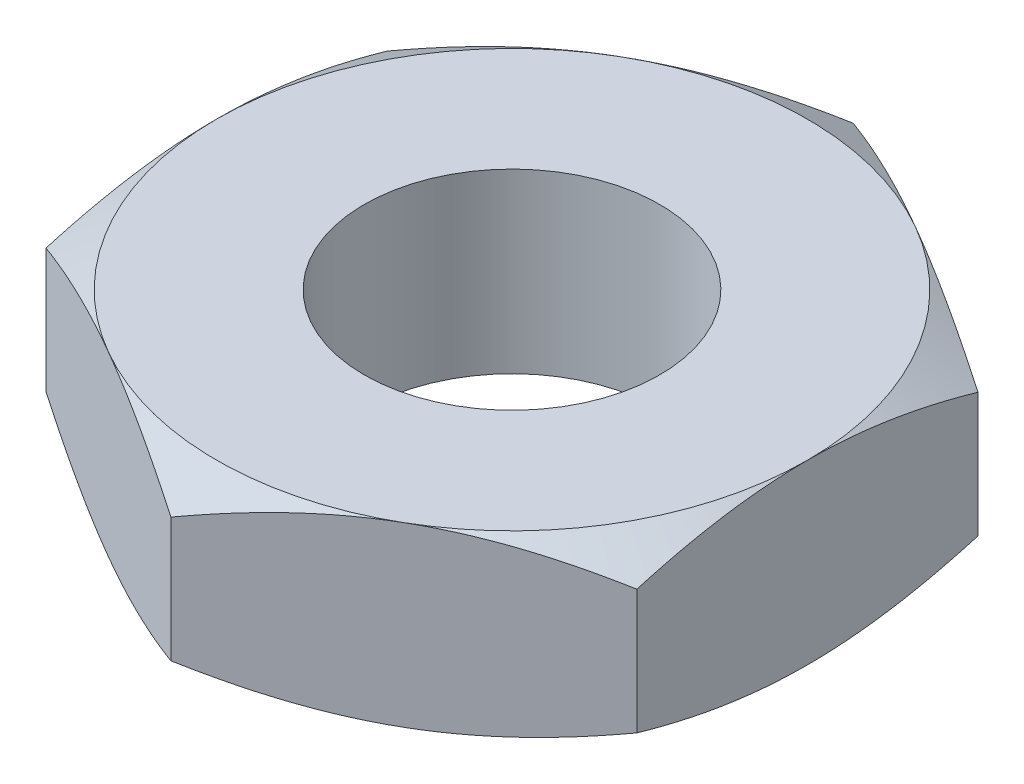
SolidWorks part; units mm, degrees
material "AISI 304"
ref_plane "Front Plane" through (0, 0, 0) normal (0, 0, 1) x (1, 0, 0)
ref_plane "Top Plane" through (0, 0, 0) normal (0, 1, 0) x (1, 0, 0)
ref_plane "Right Plane" through (0, 0, 0) normal (1, 0, 0) x (0, 0, -1)
sketch "Sketch1" plane through (0, 0, 0) normal (0, 1, 0) x (1, 0, 0)
  line L1 (-2, 1.1547) -> (-2, -1.1547)
  line L2 (-2, -1.1547) -> (0, -2.3094)
  line L3 (0, -2.3094) -> (2, -1.1547)
  line L4 (2, -1.1547) -> (2, 1.1547)
  line L5 (2, 1.1547) -> (0, 2.3094)
  line L6 (0, 2.3094) -> (-2, 1.1547)
  circle A0 centre (0, 0) radius 2 construction
  circle A1 centre (0, 0) radius 1
  dimension "Thread Size" = 2
  dimension "Hex" = 4
extrude "Boss-Extrude1" add sketch "Sketch1" along normal mid plane 1.2
sketch "Sketch2" plane through (0, 0.6, 0) normal (0, 1, 0) x (1, 0, 0)
  circle A0 centre (0, 0) radius 1 construction
  circle A1 centre (0, 0) radius 1
curve "Helix/Spiral1" [suppressed] pitch 0.4 height 1.6 turns 4 parameters "Pitch"=0.4
sketch "Sketch3" plane through (0, 0, 0) normal (1, 0, 0) x (0, 0, -1)
  line L0 (0.7402, 0.8) -> (1, 0.95)
  line L1 (1, 0.95) -> (1, 0.6)
  line L2 (1, 0.6) -> (0.7402, 0.75)
  line L3 (0.7402, 0.75) -> (0.7402, 0.8)
  line L4 (0.8701, 0.875) -> (0.8701, 0.675) construction
  line L5 (0.7402, 0.775) -> (1, 0.775) construction
  line L6 (1, 0.6) -> (-1, 0.6) construction
  dimension "D1" = 60
  dimension "D2" = 0.05
  dimension "D3" = 0.2
sweep "Sweep1" [suppressed] add profiles "Sketch3" path "Helix/Spiral1"
sketch "Sketch4" plane through (0, 0.6, 0) normal (0, 1, 0) x (1, 0, 0)
  circle A1 centre (0, 0) radius 1
  circle A2 centre (0, 0) radius 1
  dimension "D1" = 0
extrude "Cut-Extrude1" [suppressed] cut sketch "Sketch4" along normal through all and the other way through all draft 45
sketch "Sketch5" plane through (0, 0.6, 0) normal (0, 1, 0) x (1, 0, 0)
  circle A0 centre (0, 0) radius 2 construction
  circle A1 centre (0, 0) radius 2
extrude "Cut-Extrude2" cut sketch "Sketch5" against normal through all draft 60 flip side to cut
mirror "Mirror1" about plane through (0, 0, 0) normal (0, 1, 0) of "Cut-Extrude2", "Cut-Extrude1"
equation "\"D2@Sketch3\" = \"Pitch@Helix/Spiral1\"*.125"
equation "\"D3@Sketch3\" = \"Pitch@Helix/Spiral1\"*.5"
equation "\"D3@Helix/Spiral1\" = \"Height@Boss-Extrude1\"+\"Pitch@Helix/Spiral1\""
